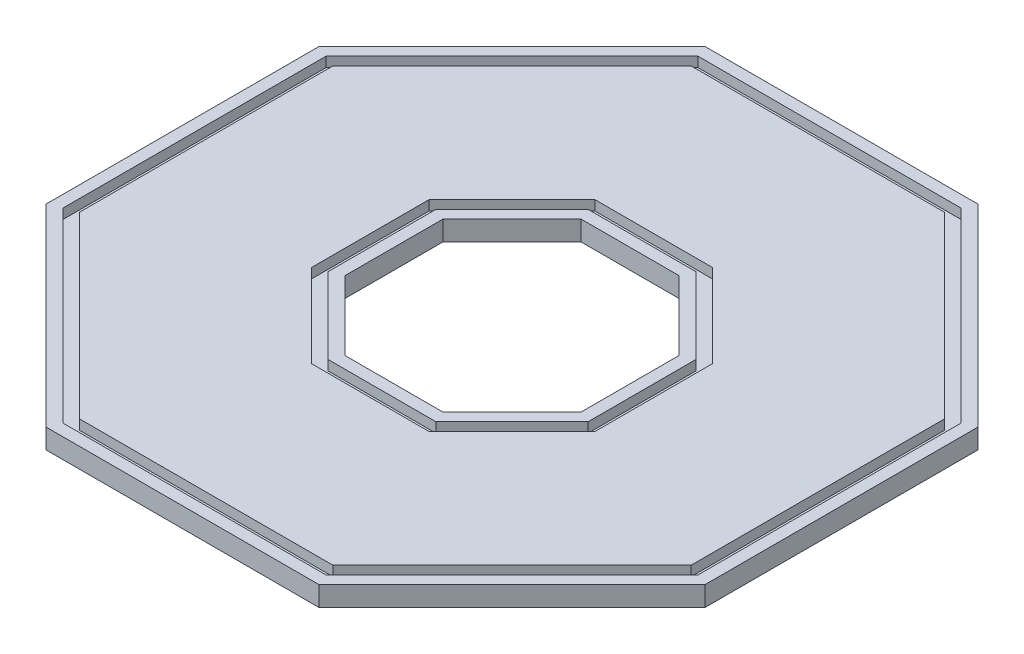
SolidWorks part; units mm, degrees
note: The reader was unsure of these and kept them because the rebuilt part matched: shared geometry of "스케치3<3>".
other "마크업1"
sketch "스케치4" plane through (-34.9216, 3, 34.9216) normal (-0.0197, 0.8267, 0.5624) x (0.9998, 0.0128, 0.0162)
ref_plane "정면" through (0, 0, 0) normal (0, 0, 1) x (1, 0, 0)
ref_plane "윗면" through (0, 0, 0) normal (0, 1, 0) x (1, 0, 0)
ref_plane "우측면" through (0, 0, 0) normal (1, 0, 0) x (0, 0, -1)
sketch "스케치1" plane through (0, 0, 0) normal (0, 1, 0) x (1, 0, 0)
  line L0 (-55, 0) -> (55, 0) construction
  line L1 (13.2795, -32.0597) -> (32.0597, -13.2795)
  line L2 (32.0597, -13.2795) -> (32.0597, 13.2795)
  line L3 (32.0597, 13.2795) -> (13.2795, 32.0597)
  line L4 (13.2795, 32.0597) -> (-13.2795, 32.0597)
  line L5 (-13.2795, 32.0597) -> (-32.0597, 13.2795)
  line L6 (-32.0597, 13.2795) -> (-32.0597, -13.2795)
  line L7 (-32.0597, -13.2795) -> (-13.2795, -32.0597)
  line L8 (-13.2795, -32.0597) -> (13.2795, -32.0597)
  line L9 (13.7766, -33.2597) -> (33.2597, -13.7766)
  line L10 (33.2597, -13.7766) -> (33.2597, 13.7766)
  line L11 (33.2597, 13.7766) -> (13.7766, 33.2597)
  line L12 (13.7766, 33.2597) -> (-13.7766, 33.2597)
  line L13 (-13.7766, 33.2597) -> (-33.2597, 13.7766)
  line L14 (-33.2597, 13.7766) -> (-33.2597, -13.7766)
  line L15 (-33.2597, -13.7766) -> (-13.7766, -33.2597)
  line L16 (-13.7766, -33.2597) -> (13.7766, -33.2597)
  circle A0 centre (0, 0) radius 34.7011 construction
  dimension "D1" = 72
  dimension "D2" = 1.2
extrude "보스-돌출1" add sketch "스케치1" along normal blind 2 contours L7 L8 L1 L2 L3 L4 L5 L6 | L15 L16 L9 L10 L11 L12 L13 L14 L8 L7 L6 L5 L4 L3 L2 L1
sketch "스케치2" plane through (0, 2, 0) normal (0, 1, 0) x (1, 0, 0)
  line L32 (-30.8597, -12.7825) -> (-12.7825, -30.8597)
  line L33 (-12.7825, -30.8597) -> (12.7825, -30.8597)
  line L34 (12.7825, -30.8597) -> (30.8597, -12.7825)
  line L35 (30.8597, -12.7825) -> (30.8597, 12.7825)
  line L36 (30.8597, 12.7825) -> (12.7825, 30.8597)
  line L37 (12.7825, 30.8597) -> (-12.7825, 30.8597)
  line L38 (-12.7825, 30.8597) -> (-30.8597, 12.7825)
  line L39 (-30.8597, 12.7825) -> (-30.8597, -12.7825)
  line L40 (-32.0597, -13.2795) -> (-13.2795, -32.0597)
  line L41 (-13.2795, -32.0597) -> (13.2795, -32.0597)
  line L42 (13.2795, -32.0597) -> (32.0597, -13.2795)
  line L43 (32.0597, -13.2795) -> (32.0597, 13.2795)
  line L44 (32.0597, 13.2795) -> (13.2795, 32.0597)
  line L45 (13.2795, 32.0597) -> (-13.2795, 32.0597)
  line L46 (-13.2795, 32.0597) -> (-32.0597, 13.2795)
  line L47 (-32.0597, 13.2795) -> (-32.0597, -13.2795)
  line L48 (-32.0597, -13.2795) -> (-13.2795, -32.0597)
  line L49 (-13.2795, -32.0597) -> (13.2795, -32.0597)
  line L50 (13.2795, -32.0597) -> (32.0597, -13.2795)
  line L51 (32.0597, -13.2795) -> (32.0597, 13.2795)
  line L52 (32.0597, 13.2795) -> (13.2795, 32.0597)
  line L53 (13.2795, 32.0597) -> (-13.2795, 32.0597)
  line L54 (-13.2795, 32.0597) -> (-32.0597, 13.2795)
  line L55 (-32.0597, 13.2795) -> (-32.0597, -13.2795)
  dimension "D1" = 1.2
  dimension "D2" = 1.2
extrude "컷-돌출1" cut sketch "스케치2" against normal blind 1
sketch "스케치3" plane through (0, 2, 0) normal (0, 1, 0) x (1, 0, 0)
  line L0 (-30.8597, 12.7825) -> (-30.8597, -12.7825) construction
  line L1 (5.9316, -14.3201) -> (14.3201, -5.9316)
  line L2 (14.3201, -5.9316) -> (14.3201, 5.9316)
  line L3 (14.3201, 5.9316) -> (5.9316, 14.3201)
  line L4 (5.9316, 14.3201) -> (-5.9316, 14.3201)
  line L5 (-5.9316, 14.3201) -> (-14.3201, 5.9316)
  line L6 (-14.3201, 5.9316) -> (-14.3201, -5.9316)
  line L7 (-14.3201, -5.9316) -> (-5.9316, -14.3201)
  line L8 (-5.9316, -14.3201) -> (5.9316, -14.3201)
  line L9 (5.4345, -13.1201) -> (13.1201, -5.4345)
  line L10 (13.1201, -5.4345) -> (13.1201, 5.4345)
  line L11 (13.1201, 5.4345) -> (5.4345, 13.1201)
  line L12 (5.4345, 13.1201) -> (-5.4345, 13.1201)
  line L13 (-5.4345, 13.1201) -> (-13.1201, 5.4345)
  line L14 (-13.1201, 5.4345) -> (-13.1201, -5.4345)
  line L15 (-13.1201, -5.4345) -> (-5.4345, -13.1201)
  line L16 (-5.4345, -13.1201) -> (5.4345, -13.1201)
  line L17 (4.9375, -11.9201) -> (11.9201, -4.9375)
  line L18 (11.9201, -4.9375) -> (11.9201, 4.9375)
  line L19 (11.9201, 4.9375) -> (4.9375, 11.9201)
  line L20 (4.9375, 11.9201) -> (-4.9375, 11.9201)
  line L21 (-4.9375, 11.9201) -> (-11.9201, 4.9375)
  line L22 (-11.9201, 4.9375) -> (-11.9201, -4.9375)
  line L23 (-11.9201, -4.9375) -> (-4.9375, -11.9201)
  line L24 (-4.9375, -11.9201) -> (4.9375, -11.9201)
  circle A0 centre (0, 0) radius 14.3201 construction
  dimension "D1" = 31
  dimension "D2" = 1.2
  dimension "D3" = 1.2
extrude "컷-돌출2" cut sketch "스케치3" against normal blind 1 contours L7 L8 L1 L2 L3 L4 L5 L6 L16 L15 L14 L13 L12 L11 L10 L9
extrude "컷-돌출3" cut sketch "스케치3<3>" against normal blind 3
sketch "스케치3<3>" plane through (0, 2, 0) normal (0, 1, 0) x (1, 0, 0) same geometry as "스케치3"
